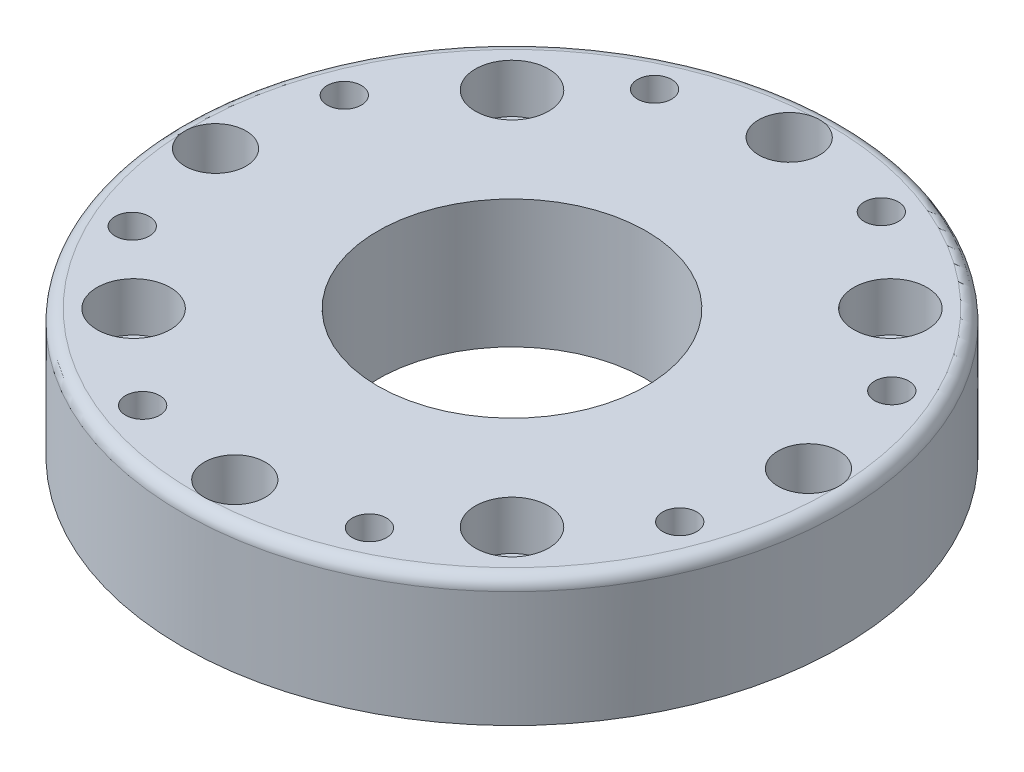
SolidWorks part; units mm, degrees
ref_plane "Front Plane" through (0, 0, 0) normal (1, 0, 0) x (0, 1, 0)
ref_plane "Top Plane" through (0, 0, 0) normal (0, 0, 1) x (0, 1, 0)
ref_plane "Right Plane" through (0, 0, 0) normal (0, 1, 0) x (-1, 0, 0)
sketch "Sketch2" plane through (0, 693.8689, 0) normal (0, 1, 0) x (-1, 0, 0)
  circle A0 centre (-1181.7984, 915.0676) radius 27
extrude "Boss-Extrude1" add sketch "Sketch2" along normal blind 10.5
sketch "Sketch3" plane through (0, 704.3689, 0) normal (0, 1, 0) x (-1, 0, 0)
  line L1 (-1197.2984, 930.5676) -> (-1166.2984, 930.5676)
  line L2 (-1197.2984, 930.5676) -> (-1197.2984, 899.5676)
  line L3 (-1197.2984, 899.5676) -> (-1166.2984, 899.5676)
  line L4 (-1166.2984, 930.5676) -> (-1166.2984, 899.5676)
  line L5 (-1197.2984, 930.5676) -> (-1166.2984, 899.5676) construction
  line L6 (-1197.2984, 899.5676) -> (-1166.2984, 930.5676) construction
  circle A0 centre (-1197.2984, 930.5676) radius 1.6
  circle A1 centre (-1166.2984, 930.5676) radius 1.6
  circle A2 centre (-1197.2984, 899.5676) radius 1.6
  circle A3 centre (-1166.2984, 899.5676) radius 1.6
  circle A5 centre (-1197.2984, 930.5676) radius 3
  circle A6 centre (-1166.2984, 930.5676) radius 3
  circle A7 centre (-1197.2984, 899.5676) radius 3
  circle A8 centre (-1166.2984, 899.5676) radius 3
  point P0 (-1181.7984, 915.0676)
  dimension "D1" = 31
  dimension "D2" = 31
extrude "Nema_Mounts_holes_M3" cut sketch "Sketch3" against normal up to surface (10.5 mm away) contours A0 | A1 | A3 | A2 up to face at (1181.7984, 693.8689, 942.0676)
extrude "Nema_Mount_holes_cap_6mm" cut sketch "Sketch3<4>" against normal blind 4 contours A5 | A6 | A7 | A8
sketch "Sketch3<4>" plane through (0, 704.3689, 0) normal (0, 1, 0) x (-1, 0, 0) same geometry as "Sketch3"
sketch "Sketch5" plane through (0, 704.3689, 0) normal (0, 1, 0) x (-1, 0, 0)
  circle A0 centre (-1160.4015, 924.7847) radius 1.4
  circle A1 centre (-1159.7975, 906.8087) radius 1.4
  circle A2 centre (-1172.0814, 893.6707) radius 1.4
  circle A3 centre (-1190.0573, 893.0667) radius 1.4
  circle A4 centre (-1203.1954, 905.3506) radius 1.4
  circle A5 centre (-1203.7994, 923.3265) radius 1.4
  circle A6 centre (-1191.5155, 936.4646) radius 1.4
  circle A7 centre (-1173.5395, 937.0686) radius 1.4
  point P20 (-1181.7984, 915.0676)
  dimension "D1" = 23.5
  dimension "D2" = 2.8
  dimension "D3" = 8
extrude "Reducer_Holes_M2.5" cut sketch "Sketch5" against normal up to surface (10.5 mm away) up to face at (1197.2984, 693.8689, 901.1676)
sketch "Sketch6" plane through (0, 693.8689, 0) normal (0, -1, 0) x (1, 0, 0)
  line L0 (1176.2363, 938.0985) -> (1173.996, 939.919)
  line L1 (1162.0943, 922.4464) -> (1163.273, 925.0816)
  line L2 (1163.273, 925.0816) -> (1161.5801, 927.4199)
  line L3 (1161.5801, 927.4199) -> (1158.7087, 927.123)
  line L4 (1158.7087, 927.123) -> (1157.5301, 924.4878)
  line L5 (1157.5301, 924.4878) -> (1159.2229, 922.1495)
  line L6 (1159.2229, 922.1495) -> (1162.0943, 922.4464)
  line L7 (1173.996, 939.919) -> (1171.2992, 938.8891)
  line L8 (1171.2992, 938.8891) -> (1170.8428, 936.0386)
  line L9 (1170.8428, 936.0386) -> (1173.0831, 934.2181)
  line L10 (1173.0831, 934.2181) -> (1175.7799, 935.2481)
  line L11 (1175.7799, 935.2481) -> (1176.2363, 938.0985)
  line L12 (1194.1507, 935.2859) -> (1193.8538, 938.1574)
  line L13 (1193.8538, 938.1574) -> (1191.2186, 939.336)
  line L14 (1191.2186, 939.336) -> (1188.8803, 937.6432)
  line L15 (1188.8803, 937.6432) -> (1189.1772, 934.7718)
  line L16 (1189.1772, 934.7718) -> (1191.8124, 933.5931)
  line L17 (1191.8124, 933.5931) -> (1194.1507, 935.2859)
  line L18 (1204.8293, 920.6298) -> (1206.6498, 922.8701)
  line L19 (1206.6498, 922.8701) -> (1205.6199, 925.5669)
  line L20 (1205.6199, 925.5669) -> (1202.7694, 926.0233)
  line L21 (1202.7694, 926.0233) -> (1200.9489, 923.783)
  line L22 (1200.9489, 923.783) -> (1201.9789, 921.0862)
  line L23 (1201.9789, 921.0862) -> (1204.8293, 920.6298)
  line L24 (1202.0167, 902.7154) -> (1204.8882, 903.0123)
  line L25 (1204.8882, 903.0123) -> (1206.0668, 905.6474)
  line L26 (1206.0668, 905.6474) -> (1204.374, 907.9857)
  line L27 (1204.374, 907.9857) -> (1201.5026, 907.6889)
  line L28 (1201.5026, 907.6889) -> (1200.3239, 905.0537)
  line L29 (1200.3239, 905.0537) -> (1202.0167, 902.7154)
  line L30 (1187.3606, 892.0368) -> (1189.6009, 890.2163)
  line L31 (1189.6009, 890.2163) -> (1192.2977, 891.2462)
  line L32 (1192.2977, 891.2462) -> (1192.7541, 894.0967)
  line L33 (1192.7541, 894.0967) -> (1190.5138, 895.9172)
  line L34 (1190.5138, 895.9172) -> (1187.817, 894.8872)
  line L35 (1187.817, 894.8872) -> (1187.3606, 892.0368)
  line L36 (1169.4462, 894.8493) -> (1169.7431, 891.9779)
  line L37 (1169.7431, 891.9779) -> (1172.3782, 890.7993)
  line L38 (1172.3782, 890.7993) -> (1174.7166, 892.4921)
  line L39 (1174.7166, 892.4921) -> (1174.4197, 895.3635)
  line L40 (1174.4197, 895.3635) -> (1171.7845, 896.5422)
  line L41 (1171.7845, 896.5422) -> (1169.4462, 894.8493)
  line L42 (1158.7676, 909.5055) -> (1156.9471, 907.2652)
  line L43 (1156.9471, 907.2652) -> (1157.977, 904.5684)
  line L44 (1157.977, 904.5684) -> (1160.8275, 904.112)
  line L45 (1160.8275, 904.112) -> (1162.648, 906.3523)
  line L46 (1162.648, 906.3523) -> (1161.618, 909.0491)
  line L47 (1161.618, 909.0491) -> (1158.7676, 909.5055)
  circle A0 centre (1160.4015, 924.7847) radius 2.5 construction
  point P1 (1158.1194, 925.8054)
  point P54 (1181.7984, 915.0676)
  dimension "D1" = 5
  dimension "D2" = 8
extrude "Reducer_Nuts_M2.5" cut sketch "Sketch6" against normal blind 4
sketch "Sketch9" plane through (0, 693.8689, 0) normal (0, -1, 0) x (-1, 0, 0)
  circle A1 centre (-1181.7984, -915.0676) radius 11
  dimension "D1" = 22
extrude "Shaft_skirt_22mm" cut sketch "Sketch9" against normal up to surface (10.5 mm away) up to face at (1173.5395, 704.3689, 938.4686)
fillet "Fillet1" radius 1 1 edges at (1181.7984, 704.3689, 942.0676)
sketch "Sketch10" plane through (0, 693.8689, 0) normal (0, -1, 0) x (1, 0, 0)
  line L0 (1172.1395, 937.0686) -> (1192.9155, 936.4646) construction
  line L1 (1192.9155, 936.4646) -> (1182.5275, 936.7666) construction
  line L2 (1182.5275, 936.7666) -> (1182.7058, 942.0524) construction
  circle A0 centre (1182.5883, 938.5676) radius 2.5
  circle A1 centre (1181.7984, 915.0676) radius 27 construction
  circle A2 centre (1173.5395, 937.0686) radius 1.4 construction
  circle A3 centre (1191.5155, 936.4646) radius 1.4 construction
  circle A4 centre (1205.2984, 914.2778) radius 2.5
  circle A5 centre (1181.0086, 891.5676) radius 2.5
  circle A6 centre (1158.2984, 915.8575) radius 2.5
  point P21 (1181.7984, 915.0676)
  dimension "D1" = 23.5
  dimension "D2" = 4
sketch "Sketch11" plane through (0, 693.8689, 0) normal (0, -1, 0) x (-1, 0, 0)
  point P0 (-1173.5395, -937.0686)
  point P1 (-1191.5155, -936.4646)
extrude "Cut-Extrude1" cut sketch "Sketch10" along normal blind 5 from surface starting at face at (1181.7984, 704.3689, 941.0676)
fillet "Fillet3" radius 1 4 edges at (1205.2984, 699.3689, 916.7778) (1181.0086, 699.3689, 894.0676) (1158.2984, 699.3689, 918.3575) (1182.5883, 699.3689, 941.0676)
